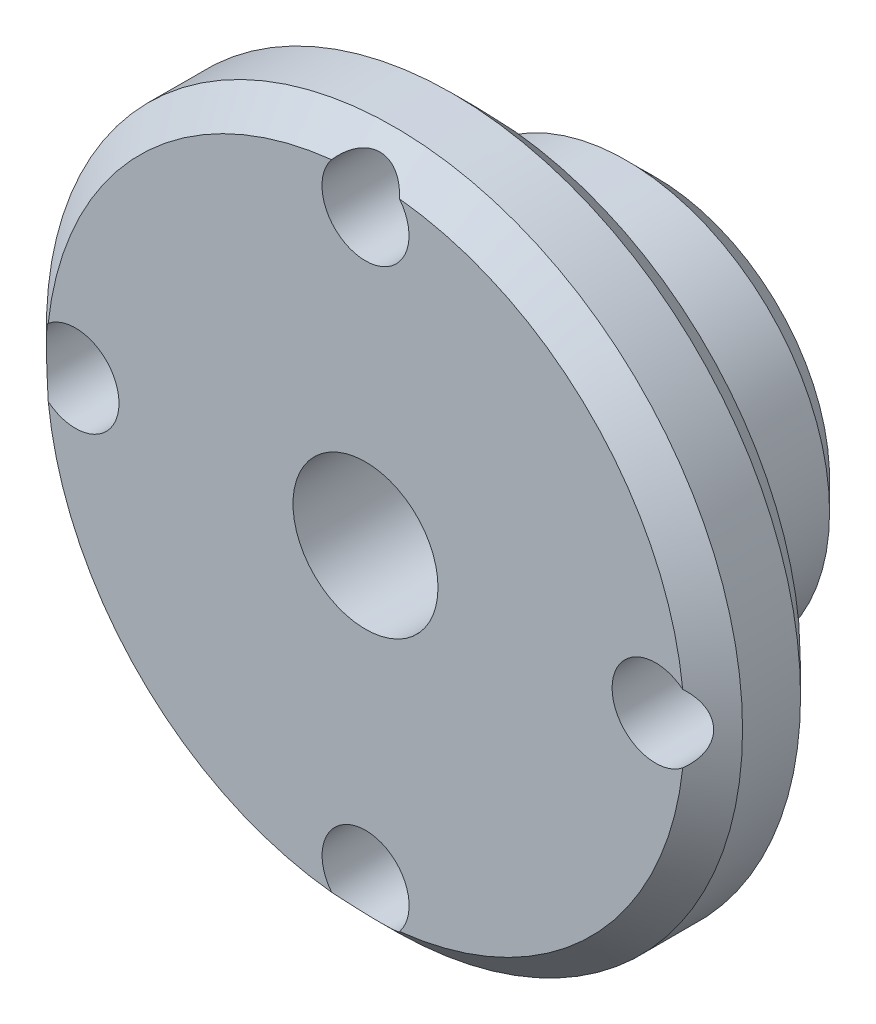
SolidWorks part; units mm, degrees
ref_plane "前视基准面" through (0, 0, 0) normal (0, 0, 1) x (1, 0, 0)
ref_plane "上视基准面" through (0, 0, 0) normal (0, 1, 0) x (1, 0, 0)
ref_plane "右视基准面" through (0, 0, 0) normal (1, 0, 0) x (0, 0, -1)
other "Configuration Table"
sketch "Sketch1" plane through (0, 0, 0) normal (0, 0, 1) x (1, 0, 0)
  circle A0 centre (0, 0) radius 6
  dimension "D1" = 12
extrude "Boss-Extrude1" add sketch "Sketch1" along normal blind 2
sketch "Sketch2" plane through (0, 0, 0) normal (0, 0, -1) x (-1, 0, 0)
  circle A0 centre (0, 0) radius 3.5
  circle A1 centre (0, 0) radius 2.5
  dimension "D1" = 7
  dimension "D2" = 5
extrude "Boss-Extrude2" add sketch "Sketch2" along normal blind 3
sketch "Sketch3" plane through (0, 0, 2) normal (0, 0, 1) x (1, 0, 0)
  circle A0 centre (0, 0) radius 5 construction
  circle A1 centre (0, 5) radius 0.75
  circle A2 centre (0.001, 0.001) radius 5 construction
  circle A3 centre (5.001, 0.001) radius 0.75
  circle A4 centre (0.002, 0) radius 5 construction
  circle A5 centre (0.002, -5) radius 0.75
  circle A6 centre (0.001, -0.001) radius 5 construction
  circle A7 centre (-4.999, -0.001) radius 0.75
  point P20 (0.001, 0)
  dimension "D1" = 1.5
  dimension "D2" = 10
  dimension "D3" = 4
extrude "Cut-Extrude1" cut sketch "Sketch3" against normal blind 2.5
chamfer "Chamfer1" distance 0.5 angle 45 3 edges at (-3.5, 0, -3) (6, 0, 2) (6, 0, 0)
sketch "Sketch5" plane through (0, 0, 2) normal (0, 0, 1) x (1, 0, 0)
  circle A0 centre (0, 0) radius 1.25
  dimension "D1" = 2.5
extrude "Cut-Extrude3" cut sketch "Sketch5" against normal through all
